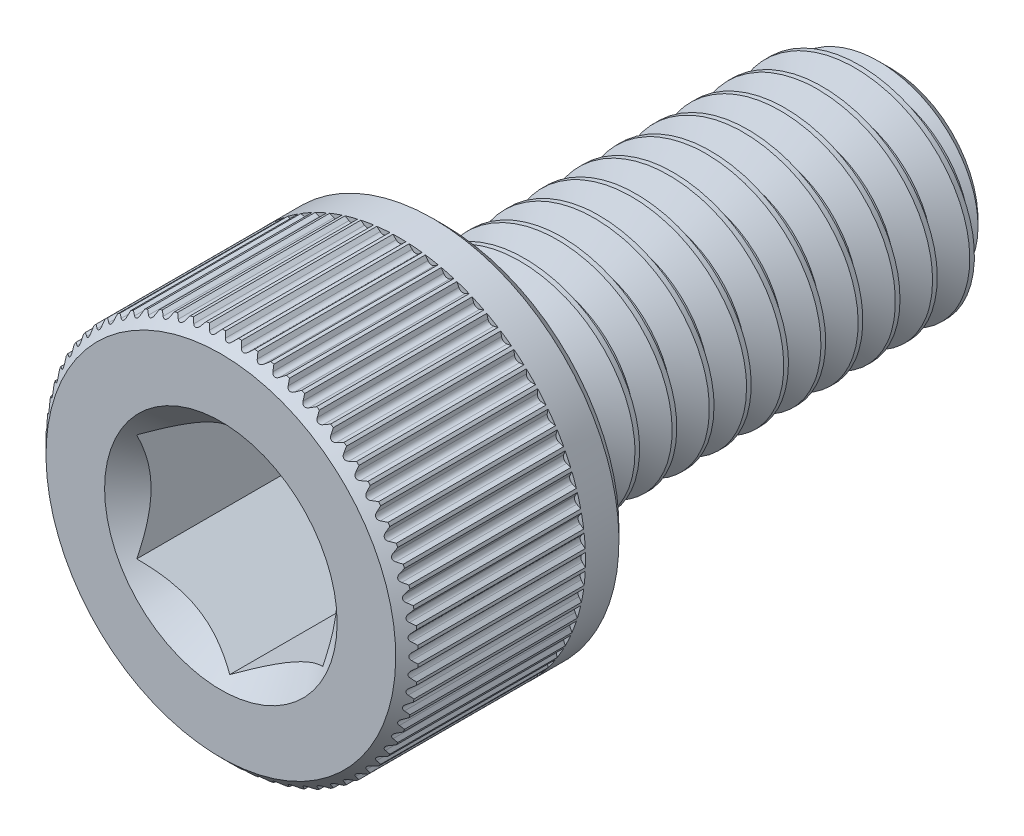
SolidWorks part; units mm, degrees
ref_plane "Front Plane" through (0, 0, 0) normal (0, 0, 1) x (1, 0, 0)
ref_plane "Top Plane" through (0, 0, 0) normal (0, 1, 0) x (1, 0, 0)
ref_plane "Right Plane" through (0, 0, 0) normal (1, 0, 0) x (0, 0, -1)
sketch "Sketch1" plane through (0, 0, 0) normal (1, 0, 0) x (0, 0, -1)
  line L0 (-9, 0) -> (9, 0) construction
  line L1 (9, 0) -> (9, 2.3505) construction
  line L2 (9, 2.3505) -> (8.3505, 3) construction
  line L3 (8.3505, 3) -> (8.25, 3) construction
  line L4 (8.25, 3) -> (-3, 3) construction
  line L5 (-3, 3) -> (-3, 5) construction
  line L6 (-3, 5) -> (-9, 5) construction
  line L7 (-9, 5) -> (-9, 0) construction
  line L8 (9, 2.3505) -> (9, 3) construction
  line L9 (8.9375, 3.1083) -> (9.4375, 2.2422) construction
  line L10 (9.4375, 2.2422) -> (9.9375, 3.1083) construction
  line L11 (9.9375, 3.1083) -> (8.9375, 3.1083) construction
  line L12 (9.4375, 3.1083) -> (9.4375, 3) construction
  line L13 (9.4375, 2.2422) -> (9.4375, 2.3505) construction
  line L14 (9.375, 2.3505) -> (9.5, 2.3505) construction
  line L15 (9, 3) -> (9.875, 3) construction
  line L16 (8.9687, 3.0541) -> (9.9063, 3.0541) construction
  line L17 (9, 0) -> (9, -3) construction
  line L18 (-3.3, 5) -> (-3, 4.7) construction
  line L19 (-8.7, 5) -> (-9, 4.7) construction
  line L20 (-3, 3) -> (-3, 0) construction
  line L21 (-3, 1.5) -> (1, 1.5) construction
  line L22 (1, 1.5) -> (5, 1.5) construction
  line L23 (5, 1.5) -> (9, 1.5) construction
  line L24 (1, 1.5) -> (1, 3) construction
  line L25 (1, 3) -> (1, 5) construction
  line L26 (5, 1.5) -> (5, 5) construction
  point P0 (-9, 2.5)
  point P3 (6.5, 3)
  point P4 (0, 0)
  point P18 (5, 3)
  point P22 (9.4375, 2.3505)
  point P24 (8.25, 3)
  point P25 (9.4375, 3)
  point P28 (9.4375, 3.0541)
  point P29 (6.5, -3)
  point P30 (1, 3)
  point P31 (-6, 5)
  point P37 (-4.05, 5)
  point P38 (-8.55, 5)
  point P45 (1, 1.5)
  point P46 (5, 1.5)
  dimension "D2" = 0.125
  dimension "D7" = 0.3
  dimension "D8" = 0.3
  dimension "D9" = 0.3
  dimension "D10" = 0.15
  dimension "D11" = 0.75
  dimension "Drive Size" = 5
  dimension "Head Diameter" = 10
  dimension "Head Height" = 6
  dimension "Thread Pitch" = 1
  dimension "Thread Size" = 6
  dimension "Length" = 12
  dimension "D12" = 0.75
  dimension "D4" = 2.5
  dimension "D3" = 45
sketch "Sketch2" plane through (0, 0, 0) normal (1, 0, 0) x (0, 0, -1)
  line L0 (-9, 0) -> (-9, 4.7)
  line L1 (-8.7, 5) -> (-3.3, 5)
  line L2 (-3, 4.7) -> (-3, 3.3)
  line L4 (8.3505, 3) -> (9, 2.3505)
  line L5 (9, 2.3505) -> (9, 0)
  line L6 (-3, 5) -> (-9, 5) construction
  line L7 (9, 0) -> (-9, 0)
  line L8 (-8.7, 5) -> (-9, 4.7) construction
  line L10 (-8.7, 5) -> (-9, 4.7)
  line L14 (-3.3, 5) -> (-3, 4.7) construction
  line L16 (-3.3, 5) -> (-3, 4.7)
  line L17 (-3, 3) -> (-3, 5) construction
  line L19 (-2.7, 3) -> (8.3505, 3)
  line L20 (8.25, 3) -> (-3, 3) construction
  arc A1 (-3, 3.3) -> (-2.7, 3) centre (-2.7, 3.3) ccw
  dimension "D3" = 0.3
revolve "Revolve1" add sketch "Sketch2" angle 360 about L7
sketch "Sketch3" plane through (0, 0, 9) normal (0, 0, 1) x (1, 0, 0)
  line L1 (2.5, -1.4434) -> (2.5, 1.4434)
  line L2 (2.5, 1.4434) -> (0, 2.8868)
  line L3 (0, 2.8868) -> (-2.5, 1.4434)
  line L4 (-2.5, 1.4434) -> (-2.5, -1.4434)
  line L5 (-2.5, -1.4434) -> (0, -2.8868)
  line L6 (0, -2.8868) -> (2.5, -1.4434)
  circle A0 centre (0, 0) radius 2.5 construction
  circle A1 centre (0, 0) radius 5 construction
  circle A2 centre (0, 0) radius 5 construction
  circle A3 centre (0, 0) radius 2.8868 construction
  point P13 (0, 0)
extrude "Cut-Extrude1" cut sketch "Sketch3" against normal offset from surface (5 mm away) 1 up to face at (0, 4.7, 3)
sketch "Sketch4" plane through (0, 0, 9) normal (0, 0, 1) x (1, 0, 0)
  circle A0 centre (0, 0) radius 3.125
  dimension "D1" = 6.25
extrude "Cut-Extrude2" cut sketch "Sketch4" against normal up to vertex (3 mm away) draft 45 up to point (0, 5, 6)
sketch "Sketch11" plane through (0, 0, 0) normal (1, 0, 0) x (0, 0, -1)
  line L0 (-9, 0) -> (9, 0) construction
  line L1 (-9, 0) -> (9, 0) construction
  line L2 (-0.75, 0) -> (-0.75, 3) construction
  line L3 (8.25, 3) -> (-3, 3) construction
  line L4 (6.75, 0) -> (6.75, 3) construction
  line L6 (9, 2.3505) -> (9, 3) construction
  point P2 (-0.75, 0)
  point P3 (6.75, 0)
  dimension "D1" = 2.25
  dimension "D2" = 2.25
sketch "Sketch6" plane through (0, 0, -9) normal (0, 0, -1) x (-1, 0, 0)
  circle A0 centre (0, 0) radius 3
curve "Helix/Spiral1" pitch 1 height 13 turns 13
sketch "Sketch10" plane through (0, 0, 0) normal (1, 0, 0) x (0, 0, -1)
  line L0 (-2.7, -5) -> (-2.7, 5)
  line L5 (-9, 0) -> (9, 0) construction
  line L6 (-2.7, 3) -> (-2.7, -3) construction
  point P3 (-2.7, 0)
split "Split1" trim tools "Sketch10" bodies to split 106 resulting bodies 114 115
sketch "Sketch7" plane through (0, 0, 0) normal (1, 0, 0) x (0, 0, -1)
  line L0 (8.9687, 3.0541) -> (9.9063, 3.0541)
  line L1 (9.9063, 3.0541) -> (9.5, 2.3505)
  line L2 (9.5, 2.3505) -> (9.375, 2.3505)
  line L3 (9.375, 2.3505) -> (8.9687, 3.0541)
sweep "Cut-Sweep1" cut profiles "Sketch7" path "Helix/Spiral1" align with end faces yes
sketch "Sketch8" plane through (0, 0, 0) normal (1, 0, 0) x (0, 0, -1)
  line L0 (-3, 0) -> (-3, 3)
  line L1 (-2.7, -3) -> (-2.7, 3) construction
  line L2 (-3, 3) -> (-2.7, 3)
  line L4 (-2.7, 3) -> (-0.9679, 0)
  line L5 (-0.9679, 0) -> (-3, 0)
  line L6 (8.25, 3) -> (-3, 3) construction
  line L7 (-9, 0) -> (9, 0) construction
  dimension "D1" = 60
revolve "Revolve2" add sketch "Sketch8" angle 360 about L5
ref_plane "Plane1" through (0, 0, 9) normal (0, 0, 1) x (1, 0, 0)
sketch "Sketch12" plane through (0, 0, 9) normal (0, 0, 1) x (1, 0, 0)
  line L0 (0, 0) -> (0.1745, 4.997) construction
  line L1 (0, 0) -> (-0.1745, 4.997) construction
  line L2 (0, 4.875) -> (0, 5.125) construction
  line L3 (-0.3025, 5.125) -> (0.3025, 5.125)
  line L4 (-0.3025, 5.125) -> (-0.0897, 4.9122)
  line L5 (0.0897, 4.9122) -> (0.3025, 5.125)
  circle A0 centre (0, 0) radius 5 construction
  arc A1 (-0.0897, 4.9122) -> (0.0897, 4.9122) centre (0, 5.0019) ccw
  point P9 (0, 5.125)
  point P13 (0, 5)
  dimension "D2" = 0.125
  dimension "D1" = 4
extrude "Cut-Extrude3" cut sketch "Sketch12" against normal blind 4.8
pattern_circular "CirPattern1" count 72 over 360 about axis through (0, 0, 0) along (0, 0, 1) of "Cut-Extrude3"
equation "\"D2@Sketch1\" = \"Thread Pitch@Sketch1\" / 8"
equation "\"D4@Helix/Spiral1\" = \"Thread Pitch@Sketch1\""
equation "\"D7@Sketch1\" = \"Head Height@Sketch1\" * .05"
equation "\"D8@Sketch1\"=\"D7@Sketch1\""
equation "\"D9@Sketch1\"=\"D7@Sketch1\""
equation "\"D10@Sketch1\"=\"D7@Sketch1\"/2"
equation "\"D11@Sketch1\"=\"D10@Sketch1\"*5"
equation "\"D4@Sketch1\"=\"Thread Pitch@Sketch1\"*2.5"
equation "\"D12@Sketch1\"=\"Thread Pitch@Sketch1\"*.75"
equation "\"D3@Helix/Spiral1\"=\"Length@Sketch1\"+\"Thread Pitch@Sketch1\""
equation "\"D3@Sketch2\" = \"Thread Size@Sketch1\" * 0.05"
equation "\"D1@Sketch11\"=\"Length@Sketch1\"*0.1875"
equation "\"D2@Sketch11\"=\"D1@Sketch11\""
equation "\"D2@Sketch12\"=\"Head Diameter@Sketch1\"*.0125"
equation "\"D1@Cut-Extrude3\"=\"Head Height@Sketch1\"*.8"
equation "\"D1@CirPattern1\"=\"D3@CirPattern1\"/(1.25*\"D1@Sketch12\")"
equation "\"D1@Sketch4\"=\"Drive Size@Sketch1\"*1.25"
